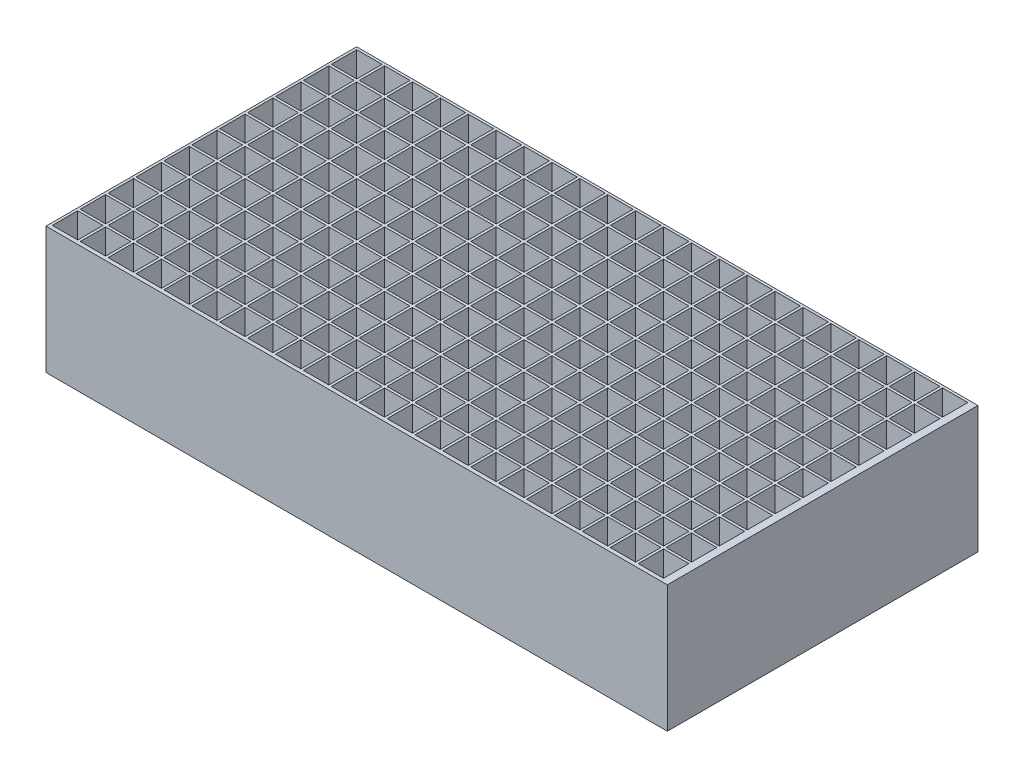
SolidWorks part; units mm, degrees
ref_plane "Front Plane" through (0, 0, 0) normal (0, 0, 1) x (1, 0, 0)
ref_plane "Top Plane" through (0, 0, 0) normal (0, 1, 0) x (1, 0, 0)
ref_plane "Right Plane" through (0, 0, 0) normal (1, 0, 0) x (0, 0, -1)
sketch "Sketch1" plane through (0, 0, 0) normal (0, 1, 0) x (1, 0, 0)
  line L1 (245, -122.5) -> (-245, -122.5)
  line L2 (245, -122.5) -> (245, 122.5)
  line L3 (245, 122.5) -> (-245, 122.5)
  line L4 (-245, -122.5) -> (-245, 122.5)
  line L5 (245, -122.5) -> (-245, 122.5) construction
  line L6 (245, 122.5) -> (-245, -122.5) construction
  point P0 (0, 0)
  dimension "D1" = 490
  dimension "D2" = 245
extrude "Boss-Extrude1" add sketch "Sketch1" along normal blind 100
sketch "Sketch2" plane through (0, 100, 0) normal (0, 1, 0) x (1, 0, 0)
  line L0 (-245, 122.5) -> (-245, -122.5) construction
  line L1 (-223, 100.5) -> (-243, 100.5)
  line L2 (-223, 100.5) -> (-223, 120.5)
  line L3 (-223, 120.5) -> (-243, 120.5)
  line L4 (-243, 100.5) -> (-243, 120.5)
  line L5 (-223, 100.5) -> (-243, 120.5) construction
  line L6 (-223, 120.5) -> (-243, 100.5) construction
  line L7 (245, 122.5) -> (-245, 122.5) construction
  point P0 (-233, 110.5)
  point P5 (-243, 110.5)
  point P8 (-233, 120.5)
  dimension "D1" = 20
  dimension "D2" = 20
  dimension "D3" = 2
  dimension "D4" = 2
extrude "Cut-Extrude1" cut sketch "Sketch2" against normal blind 95
pattern_linear "LPattern1" count 22 spacing 22 along (1, 0, 0) count 11 spacing 22 along (0, 0, 1) of "Cut-Extrude1"
sketch "Sketch3" plane through (-245, 0, 0) normal (-1, 0, 0) x (0, 0, 1)
  line L1 (-122.5, 100) -> (122.5, 100) construction
  line L2 (-122.5, 0) -> (122.5, 0) construction
  line L3 (-122.5, 50) -> (122.5, 50) construction
  line L4 (-122.5, 100) -> (-122.5, 0) construction
  line L5 (122.5, 100) -> (122.5, 0) construction
  line L6 (0, 100) -> (0, 0) construction
sketch "Sketch4" plane through (0, 0, -122.5) normal (0, 0, -1) x (-1, 0, 0)
  line L0 (0, 0) -> (0, 100) construction
  line L1 (-245, 100) -> (245, 100) construction
  line L2 (-245, 50) -> (245, 50) construction
  line L3 (-245, 100) -> (-245, 0) construction
  line L4 (245, 100) -> (245, 0) construction
